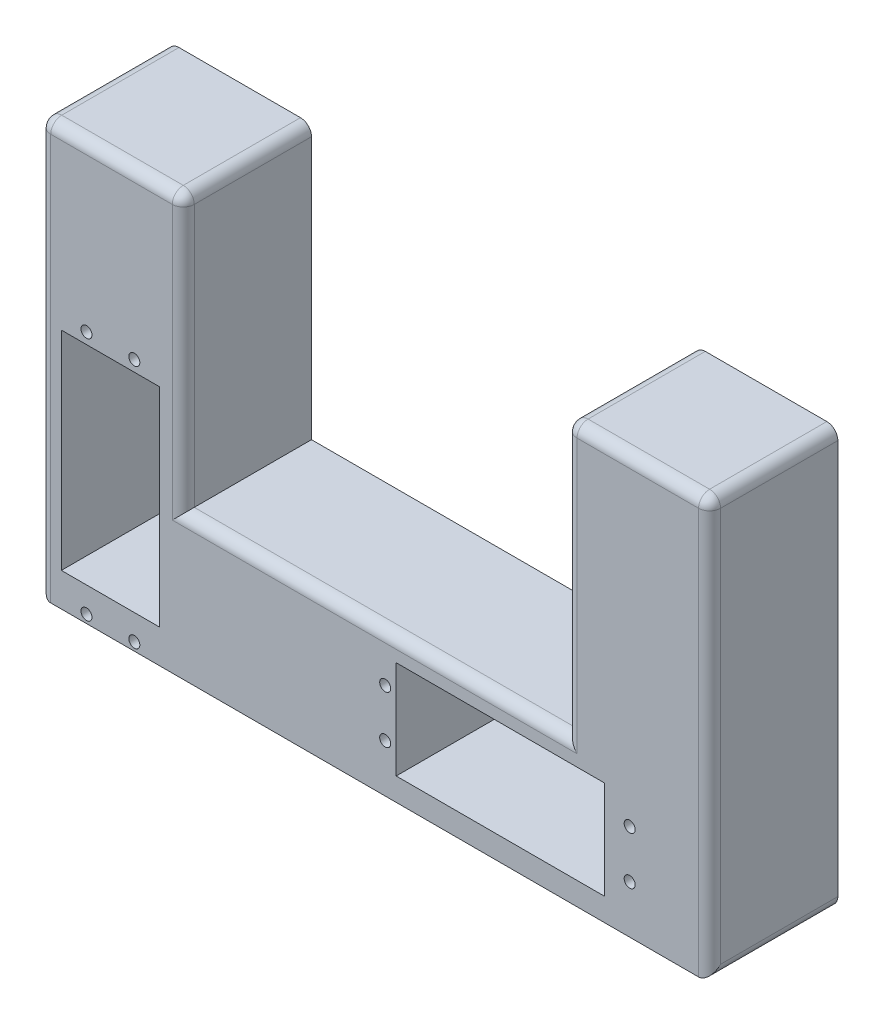
SolidWorks part; units mm, degrees
ref_plane "Front Plane" through (0, 0, 0) normal (0, 0, 1) x (1, 0, 0)
ref_plane "Top Plane" through (0, 0, 0) normal (0, 1, 0) x (1, 0, 0)
ref_plane "Right Plane" through (0, 0, 0) normal (1, 0, 0) x (0, 0, -1)
sketch "Sketch1" plane through (0, 0, 0) normal (0, 0, 1) x (1, 0, 0)
  line L1 (86.9545, 12.865) -> (116.9545, 12.865)
  line L2 (86.9545, 42.865) -> (86.9545, 100)
  line L3 (86.9545, 100) -> (116.9545, 100)
  line L4 (116.9545, 12.865) -> (116.9545, 100)
  line L5 (6.9545, 100) -> (-23.0455, 100)
  line L6 (6.9545, 100) -> (6.9545, 42.865)
  line L7 (6.9545, 12.865) -> (-23.0455, 12.865)
  line L8 (-23.0455, 100) -> (-23.0455, 12.865)
  line L9 (6.9545, 12.865) -> (86.9545, 12.865)
  line L11 (6.9545, 42.865) -> (86.9545, 42.865)
  dimension "D1" = 80
  dimension "D2" = 30
  dimension "D3" = 30
extrude "Boss-Extrude1" add sketch "Sketch1" along normal blind 26.8 contours L6 L11 L2 L3 L4 L1 L9 L7 L8 L5
sketch "Sketch2" plane through (0, 0, 26.8) normal (0, 0, 1) x (1, 0, 0)
  line L0 (46.9545, 12.865) -> (46.9545, 163.1977) construction
  line L1 (116.9545, 12.865) -> (-23.0455, 12.865) construction
  line L2 (-23.0455, 67.865) -> (116.9545, 67.865) construction
  line L3 (-23.0455, 100) -> (-23.0455, 12.865) construction
  line L4 (116.9545, 12.865) -> (116.9545, 100) construction
  line L5 (-8.0455, 100) -> (-8.0455, 12.865) construction
  line L6 (-18.5251, 63.365) -> (1.9749, 63.365)
  line L7 (-18.5251, 63.365) -> (-18.5251, 19.865)
  line L8 (-18.5251, 19.865) -> (1.9749, 19.865)
  line L9 (1.9749, 63.365) -> (1.9749, 19.865)
  line L10 (51.4545, 38.1452) -> (94.9545, 38.1452)
  line L11 (51.4545, 38.1452) -> (51.4545, 17.6452)
  line L12 (51.4545, 17.6452) -> (94.9545, 17.6452)
  line L13 (94.9545, 38.1452) -> (94.9545, 17.6452)
  line L14 (6.9545, 100) -> (-23.0455, 100) construction
  line L15 (-23.0455, 28.1455) -> (116.9545, 28.1455) construction
  dimension "D1" = 55
  dimension "D2" = 48
  dimension "D3" = 20.5
  dimension "D4" = 43.5
  dimension "D5" = 20.5
  dimension "D6" = 43.5
  dimension "D7" = 48
extrude "Cut-Extrude1" cut sketch "Sketch2" against normal through all
sketch "Sketch3" plane through (0, 0, 26.8) normal (0, 0, 1) x (1, 0, 0)
  line L0 (-18.5251, 19.865) -> (1.9749, 19.865) construction
  line L1 (-8.2751, 63.365) -> (-8.2751, -3.066) construction
  line L2 (1.9749, 63.365) -> (-18.5251, 63.365) construction
  circle A0 centre (-13.2751, 14.565) radius 1.15
  circle A1 centre (-3.2751, 14.565) radius 1.15
  circle A2 centre (-13.2751, 65.665) radius 1.15
  circle A3 centre (-3.2751, 65.665) radius 1.15
  point P14 (-12.3523, 64.9788)
  dimension "D3" = 2.3
  dimension "D4" = 2.3
  dimension "D7" = 2.3
  dimension "D1" = 5.3
  dimension "D2" = 5.3
  dimension "D5" = 10
  dimension "D6" = 5
  dimension "D8" = 2.3
  dimension "D9" = 5
extrude "Boss-Extrude2" add sketch "Sketch3" against normal through all
extrude "Cut-Extrude2" cut sketch "Sketch3<2>" against normal through all
sketch "Sketch3<2>" plane through (0, 0, 26.8) normal (0, 0, 1) x (1, 0, 0) same geometry as "Sketch3"
sketch "Sketch4" plane through (0, 0, 26.8) normal (0, 0, 1) x (1, 0, 0)
  line L0 (51.4545, 27.8952) -> (128.9839, 27.8952) construction
  line L1 (51.4545, 38.1452) -> (51.4545, 17.6452) construction
  line L2 (94.9545, 17.6452) -> (94.9545, 38.1452) construction
  circle A0 centre (100.2545, 22.8952) radius 1.15
  circle A1 centre (100.2545, 32.8952) radius 1.15
  circle A2 centre (49.1545, 22.8952) radius 1.15
  circle A3 centre (49.1545, 32.8952) radius 1.15
  dimension "D1" = 2.3
  dimension "D4" = 2.3
  dimension "D2" = 5.3
  dimension "D3" = 5
  dimension "D5" = 2.3
  dimension "D6" = 5
extrude "Cut-Extrude3" cut sketch "Sketch4" against normal through all
fillet "Fillet1" radius 2.3 13 edges at (-23.0455, 12.865, 13.4) (-23.0455, 100, 13.4) (6.9545, 100, 13.4) (86.9545, 100, 13.4) (116.9545, 100, 13.4) (116.9545, 12.865, 13.4) (101.9545, 100, 26.8) (86.9545, 71.4325, 26.8) (116.9545, 56.4325, 26.8) (46.9545, 42.865, 26.8) (6.9545, 71.4325, 26.8) (-8.0455, 100, 26.8) (-23.0455, 56.4325, 26.8)
